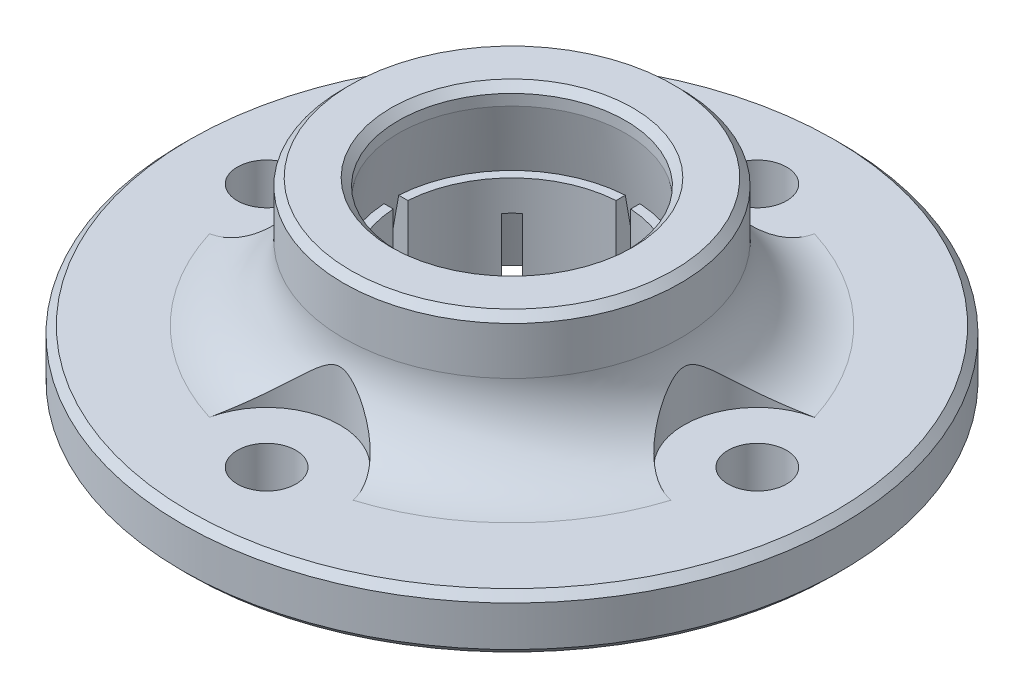
SolidWorks part; units mm, degrees
ref_plane "Front Plane" through (0, 0, 0) normal (0, 0, 1) x (1, 0, 0)
ref_plane "Top Plane" through (0, 0, 0) normal (0, 1, 0) x (1, 0, 0)
ref_plane "Right Plane" through (0, 0, 0) normal (1, 0, 0) x (0, 0, -1)
sketch "Sketch2" plane through (0, 0, 0) normal (1, 0, 0) x (0, 0, -1)
  line L0 (-3.1, 5) -> (-3.1, 4.5)
  line L1 (-3.1, 4.5) -> (-3.8935, 0)
  line L2 (-3.8935, 0) -> (-9, 0)
  line L3 (-9, 0) -> (-9, 1.5)
  line L4 (-9, 1.5) -> (-4.6, 1.5)
  line L5 (-4.6, 1.5) -> (-4.6, 5)
  line L6 (-4.6, 5) -> (-3.1, 5)
  line L7 (-7, -996.8199) -> (-7, 49003.1801) construction
  line L8 (-4.9, -996.8199) -> (-4.9, 49003.1801) construction
  line L9 (-9.1, -996.8199) -> (-9.1, 49003.1801) construction
  dimension "D1" = 9
  dimension "D2" = 3.1
  dimension "D3" = 5
  dimension "D4" = 1.5
  dimension "D7" = 7
  dimension "D8" = 1.5
  dimension "D9" = 10
  dimension "D10" = 4.5
  dimension "D5" = 2.1
  dimension "D6" = 2.1
ref_axis "Axis1" through (0, 8.4, 0) along (0, -1, 0)
revolve "Revolve1" add sketch "Sketch2" angle 360 about axis through (0, 8.4, 0) along (0, -1, 0)
sketch "Sketch3" plane through (0, 1.5, 0) normal (0, 1, 0) x (1, 0, 0)
  circle A1 centre (0, -6.7) radius 2.1 construction
  circle A2 centre (0, 0) radius 4.6 construction
  dimension "D1" = 4.2
fillet "Fillet2" radius 2 1 edges at (0, 1.5, 4.6)
hole_wizard "M2x0.4 Tapped Hole1" positions "Sketch4" profile "Sketch5" tap size "M2x0.4" standard "ANSI Metric" end condition through all
sketch "Sketch4" plane through (0, 1.5, 0) normal (0, 1, 0) x (1, 0, 0)
  point P0 (0, -6.7)
sketch "Sketch5" plane through (0, 1.5, 6.7) normal (1, 0, 0) x (0, 0, 1)
  line L0 (0, 0) -> (0, 1.5)
  line L1 (0, 1.5) -> (0.8, 1.5)
  line L2 (0.8, 1.5) -> (0.8, 0)
  line L5 (0.8, 0) -> (0, 0)
  line L11 (0, -6.35) -> (0, 107.95) construction
  dimension "Thru Tap Drill Dia." = 1.6
  dimension "Thru Tap Drill Depth" = 1.5
cosmetic thread "Hole Thread1" parameters "D2"=2
sketch "Sketch9" plane through (0, 1.5, 0) normal (0, 1, 0) x (1, 0, 0)
  circle A0 centre (0, -6.7) radius 2
  dimension "D1" = 4
extrude "Cut-Extrude1" cut sketch "Sketch9" along normal through all
pattern_circular "CirPattern1" count 4 over 360 about axis through (0, 8.4, 0) along (0, -1, 0) of "M2x0.4 Tapped Hole1", "Cut-Extrude1"
cosmetic thread "Hole Thread2" parameters "D2"=2
cosmetic thread "Hole Thread3" parameters "D2"=2
cosmetic thread "Hole Thread4" parameters "D2"=2
sketch "Sketch6" plane through (0, 0, 0) normal (0, 0, 1) x (1, 0, 0)
  line L0 (3.05, 2.8356) -> (3.05, -0.5)
  line L1 (3.05, -0.5) -> (3.8, -0.5)
  line L2 (3.8, -0.5) -> (3.8, 0)
  line L3 (3.8, 0) -> (3.3, 2.8356)
  line L4 (3.3, 2.8356) -> (3.05, 2.8356)
  line L5 (0, 8.4) -> (0, -0.4) construction
  line L6 (-3.8935, 0) -> (3.8935, 0) construction
  dimension "D1" = 3.05
  dimension "D2" = 10
  dimension "D3" = 0.5
  dimension "D4" = 3.8
  dimension "D5" = 0.25
revolve "Revolve2" add sketch "Sketch6" angle 360 about axis through (0, 8.4, 0) along (0, -1, 0)
sketch "Sketch7" plane through (0, 2.8356, 0) normal (0, 1, 0) x (1, 0, 0)
  line L0 (0, 0) -> (0, 6)
  dimension "D1" = 6
extrude "Cut-Extrude-Thin1" cut sketch "Sketch7" against normal blind 2.5 thin thin type mid plane wall 0.4
sketch "Sketch8" plane through (0, -0.5, 0) normal (0, -1, 0) x (1, 0, 0)
  line L0 (0, 0) -> (4.2426, 4.2426)
  line L1 (0, -1000) -> (0, 49000) construction
  dimension "D1" = 45
  dimension "D2" = 6
extrude "Cut-Extrude-Thin2" cut sketch "Sketch8" against normal blind 2.5 thin thin type mid plane wall 0.4
pattern_circular "CirPattern2" count 4 over 360 about axis through (0, 8.4, 0) along (0, -1, 0) of "Cut-Extrude-Thin1", "Cut-Extrude-Thin2"
chamfer "Chamfer1" distance 0.2 angle 45 5 edges at (0, 0, 3.8935) (0, 5, 3.1) (0, 1.5, 9) (0, 5, 4.6) (0, 0, 9) first distance on face at (0, 4.5, 3.1) first distance on face at (0, 5, 3.1) first distance on face at (0, 0, 9) first distance on face at (0, 3.5, 4.6) first distance on face at (6.7, 0, 0.8)
